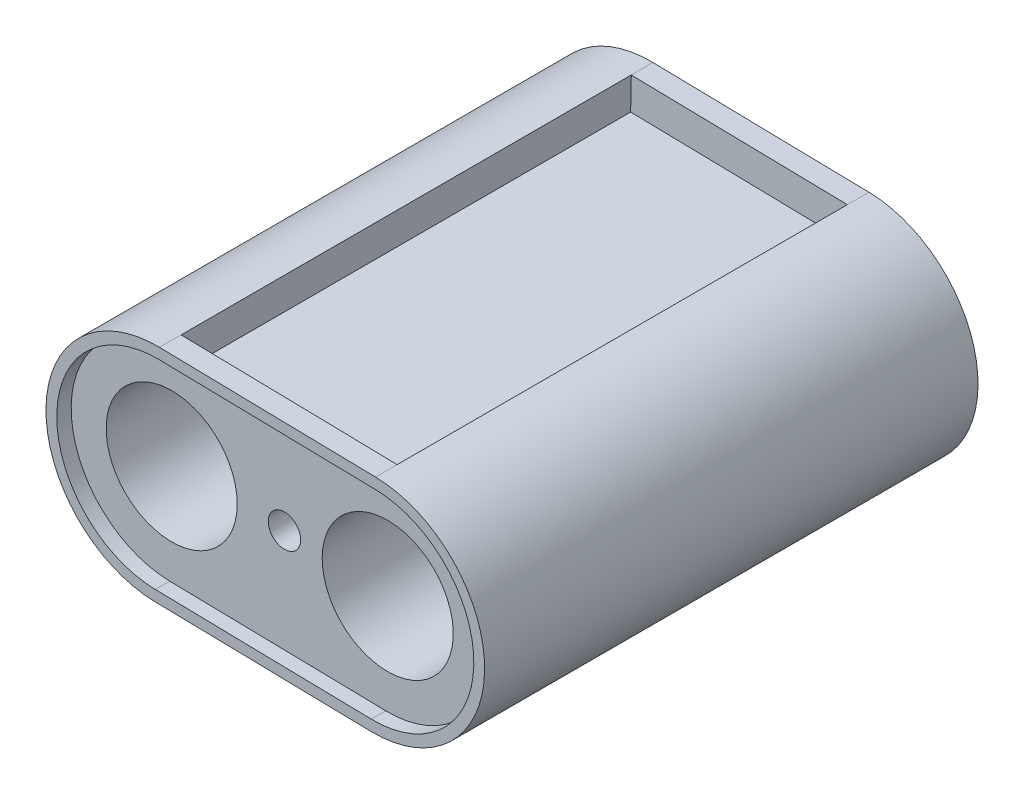
SolidWorks part; units mm, degrees
ref_plane "Спереди" through (0, 0, 0) normal (0, 0, 1) x (1, 0, 0)
ref_plane "Сверху" through (0, 0, 0) normal (0, 1, 0) x (1, 0, 0)
ref_plane "Справа" through (0, 0, 0) normal (1, 0, 0) x (0, 0, -1)
sketch "Эскиз1" plane through (0, 0, 0) normal (0, 0, 1) x (1, 0, 0)
  line L0 (0, 32.6386) -> (-1.3723, -35.9944) construction
  line L1 (-15.6574, -0.089) -> (14.3366, -0.6887) construction
  line L2 (-15.3485, 15.3597) -> (14.6455, 14.76)
  line L3 (-15.9662, -15.5377) -> (14.0278, -16.1374)
  circle A0 centre (-15.6574, -0.089) radius 9.1
  circle A1 centre (14.3366, -0.6887) radius 9.1
  arc A2 (-15.3485, 15.3597) -> (-15.9662, -15.5377) centre (-15.6574, -0.089) ccw
  arc A3 (14.0278, -16.1374) -> (14.6455, 14.76) centre (14.3366, -0.6887) ccw
  point P6 (-0.6604, -0.3889)
  dimension "D1" = 18.2
  dimension "D2" = 15
extrude "Бобышка-Вытянуть1" add sketch "Эскиз1" along normal blind 65
sketch "Эскиз2" plane through (0, 0, 65) normal (0, 0, 1) x (1, 0, 0)
  line L0 (-15.6574, -0.089) -> (14.3366, -0.6887) construction
  line L1 (-15.3785, 13.86) -> (14.6155, 13.2603)
  line L2 (-15.9363, -14.038) -> (14.0577, -14.6377)
  line L3 (14.6455, 14.76) -> (-15.3485, 15.3597) construction
  line L4 (-15.9662, -15.5377) -> (14.0278, -16.1374) construction
  line L5 (-15.9662, -15.5377) -> (14.0278, -16.1374)
  line L6 (14.6455, 14.76) -> (-15.3485, 15.3597)
  arc A0 (-15.3785, 13.86) -> (-15.9363, -14.038) centre (-15.6574, -0.089) ccw
  arc A1 (14.0577, -14.6377) -> (14.6155, 13.2603) centre (14.3366, -0.6887) ccw
  arc A2 (14.0278, -16.1374) -> (14.6455, 14.76) centre (14.3366, -0.6887) ccw construction
  arc A3 (-15.3485, 15.3597) -> (-15.9662, -15.5377) centre (-15.6574, -0.089) ccw construction
  arc A4 (14.0278, -16.1374) -> (14.6455, 14.76) centre (14.3366, -0.6887) ccw
  arc A5 (-15.3485, 15.3597) -> (-15.9662, -15.5377) centre (-15.6574, -0.089) ccw
  point P4 (-0.6604, -0.3889)
  dimension "D1" = 1.5
extrude "Бобышка-Вытянуть2" add sketch "Эскиз2" along normal blind 2
sketch "Эскиз3" plane through (0, 0, 65) normal (0, 0, 1) x (1, 0, 0)
  circle A0 centre (0, 0) radius 2.25
  dimension "D1" = 4.5
extrude "Вырез-Вытянуть1" cut sketch "Эскиз3" against normal blind 4.5
sketch "Эскиз4" plane through (0, 0, 0) normal (0, 0, -1) x (-1, 0, 0)
  circle A0 centre (0, 0) radius 2.25
  dimension "D1" = 4.5
extrude "Вырез-Вытянуть2" cut sketch "Эскиз4" against normal blind 4.5
sketch "Эскиз5" plane through (0, 0, 0) normal (0, 0, -1) x (-1, 0, 0)
  line L0 (15.6574, -0.089) -> (-14.3366, -0.6887) construction
  line L1 (15.9662, -15.5377) -> (-14.0278, -16.1374)
  line L2 (15.3485, 15.3597) -> (-14.6455, 14.76)
  line L3 (-14.3366, -0.6887) -> (15.6574, -0.089) construction
  line L4 (-14.6155, 13.2603) -> (15.3785, 13.86)
  line L5 (-14.0577, -14.6377) -> (15.9363, -14.038)
  line L6 (-14.6455, 14.76) -> (15.3485, 15.3597) construction
  arc A0 (15.9662, -15.5377) -> (15.3485, 15.3597) centre (15.6574, -0.089) ccw
  arc A1 (-14.6455, 14.76) -> (-14.0278, -16.1374) centre (-14.3366, -0.6887) ccw
  arc A2 (-14.6155, 13.2603) -> (-14.0577, -14.6377) centre (-14.3366, -0.6887) ccw
  arc A3 (15.9363, -14.038) -> (15.3785, 13.86) centre (15.6574, -0.089) ccw
  point P4 (0.6604, -0.3889)
  point P9 (0.6604, -0.3889)
  dimension "D1" = 1.5
extrude "Бобышка-Вытянуть3" add sketch "Эскиз5" along normal blind 1.5
sketch "Эскиз7" plane through (0.3008, 15.0468, 0) normal (0.02, 0.9998, 0) x (0.9998, -0.02, 0)
  line L0 (14.3475, -67) -> (-15.6525, -67) construction
  line L1 (14.3475, -64) -> (-15.6525, -64)
  line L2 (14.3475, -64) -> (14.3475, -1.5)
  line L3 (14.3475, -1.5) -> (-15.6525, -1.5)
  line L4 (-15.6525, -64) -> (-15.6525, -1.5)
  line L5 (-15.6525, 1.5) -> (14.3475, 1.5) construction
  line L6 (-15.6525, -67) -> (-15.6525, 1.5) construction
  line L7 (14.3475, -67) -> (14.3475, 1.5) construction
  dimension "D1" = 3
  dimension "D2" = 3
extrude "Вырез-Вытянуть4" cut sketch "Эскиз7" against normal blind 4.5
sketch "Эскиз8" plane through (-0.3169, -15.8506, 0) normal (-0.02, -0.9998, 0) x (-0.9998, 0.02, 0)
  line L0 (15.6525, -67) -> (15.6525, 1.5) construction
  line L1 (15.6525, -1.5) -> (-14.3475, -1.5)
  line L2 (15.6525, -1.5) -> (15.6525, -64)
  line L3 (15.6525, -64) -> (-14.3475, -64)
  line L4 (-14.3475, -1.5) -> (-14.3475, -64)
  line L5 (-14.3475, -67) -> (-14.3475, 1.5) construction
  line L6 (-14.3475, 1.5) -> (15.6525, 1.5) construction
  line L7 (15.6525, -67) -> (-14.3475, -67) construction
  dimension "D1" = 3
  dimension "D2" = 3
extrude "Вырез-Вытянуть5" cut sketch "Эскиз8" against normal blind 4.5
